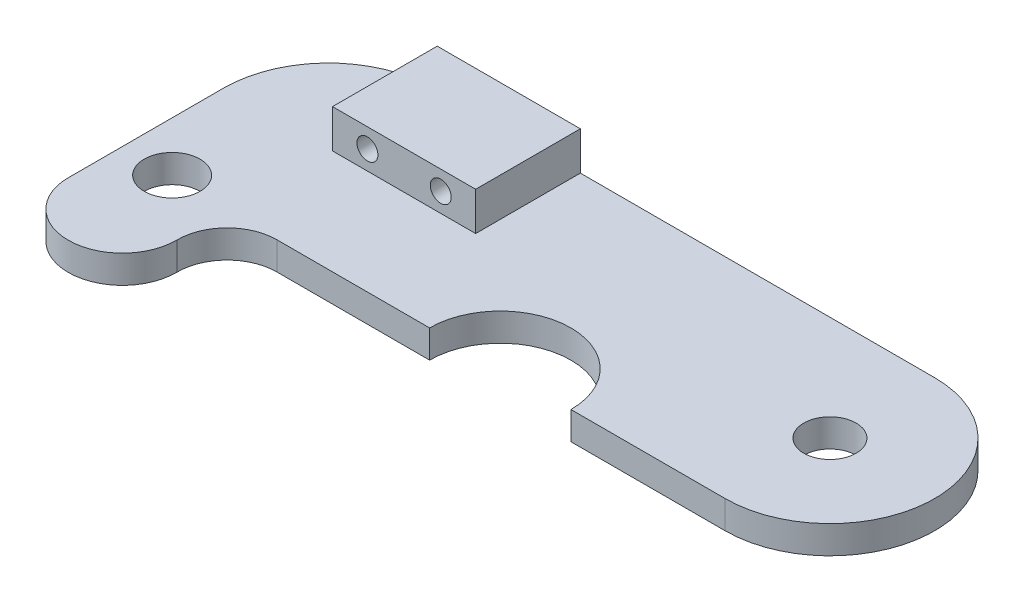
SolidWorks part; units mm, degrees
ref_plane "Front Plane" through (0, 0, 0) normal (0, 0, 1) x (1, 0, 0)
ref_plane "Top Plane" through (0, 0, 0) normal (0, 1, 0) x (1, 0, 0)
ref_plane "Right Plane" through (0, 0, 0) normal (1, 0, 0) x (0, 0, -1)
sketch "Sketch1" plane through (0, 0, 0) normal (0, 1, 0) x (1, 0, 0)
  line L0 (70.0498, -40.7752) -> (158.4495, -40.7752)
  line L1 (-126.5505, 79.2248) -> (158.4495, 79.2248)
  line L3 (-98.4502, -40.7752) -> (-10.9502, -40.7752)
  line L8 (-188.9502, -40.7752) -> (-188.9502, 19.2248)
  line L11 (-188.9502, -40.7752) -> (-188.9502, -69.7752)
  line L13 (-126.9502, -69.2752) -> (-126.9502, -69.7752)
  arc A0 (70.0498, -40.7752) -> (-10.9502, -40.7752) centre (29.5498, -40.7752) ccw
  circle A1 centre (158.4495, 19.2248) radius 15
  arc A2 (158.4495, -40.7752) -> (158.4495, 79.2248) centre (158.4495, 19.2248) ccw
  arc A3 (-126.5505, 79.2248) -> (-188.9502, 19.2248) centre (-128.9041, 19.2248) ccw
  arc A5 (-188.9502, -69.7752) -> (-126.9502, -69.7752) centre (-157.9502, -69.7752) ccw
  circle A6 centre (-160.4502, -38.7752) radius 16
  arc A7 (-98.4502, -40.7752) -> (-126.9502, -69.2752) centre (-98.4502, -69.2752) ccw
  dimension "D3" = 30
  dimension "D4" = 81
  dimension "D8" = 32
  dimension "D5" = 28.5
  dimension "D1" = 285
  dimension "D2" = 87.5
  dimension "D6" = 60
  dimension "D7" = 62
  dimension "D9" = 31
  dimension "D10" = 190
  dimension "D11" = 142.18
extrude "Boss-Extrude2" add sketch "Sketch1" along normal blind 16
scale "Scale1" scale about centroid uniform scaling yes scale factor 0.1
sketch "Sketch2" plane through (0, 8.8, 0) normal (0, 1, 0) x (1, 0, 0)
  line L1 (-13.8868, 21.7261) -> (-5.6868, 21.7261)
  line L2 (-13.8868, 21.7261) -> (-13.8868, 15.7261)
  line L3 (-13.8868, 15.7261) -> (-5.6868, 15.7261)
  line L4 (-5.6868, 21.7261) -> (-5.6868, 15.7261)
  dimension "D1" = 6
  dimension "D2" = 8.2
extrude "Boss-Extrude3" add sketch "Sketch2" along normal blind 2.2
sketch "Sketch3" plane through (0, 0, -21.7261) normal (0, 0, -1) x (-1, 0, 0)
  line L0 (5.6868, 11) -> (13.8868, 11) construction
  line L1 (5.6868, 11) -> (5.6868, 8.8) construction
  line L2 (13.8868, 11) -> (13.8868, 8.8) construction
  circle A0 centre (7.6868, 9.9) radius 0.6
  circle A1 centre (11.8868, 9.9) radius 0.6
  dimension "D1" = 1.2
  dimension "D2" = 1.2
  dimension "D3" = 1.1
  dimension "D4" = 0
  dimension "D5" = 2
  dimension "D6" = 2
extrude "Cut-Extrude1" cut sketch "Sketch3" against normal up to next
